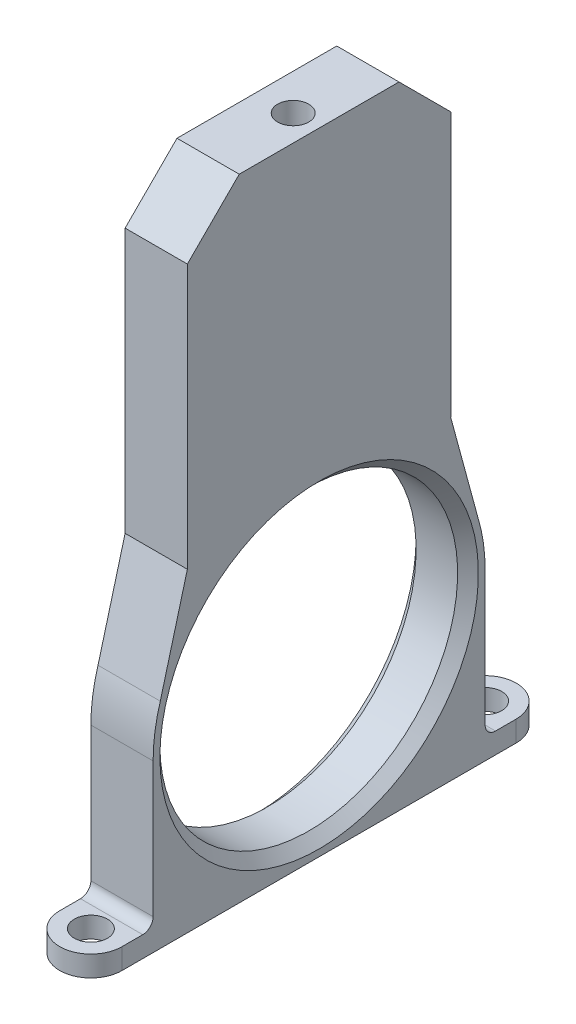
SolidWorks part; units mm, degrees
ref_plane "Front Plane" through (0, 0, 0) normal (0, 0, 1) x (1, 0, 0)
ref_plane "Top Plane" through (0, 0, 0) normal (0, 1, 0) x (1, 0, 0)
ref_plane "Right Plane" through (0, 0, 0) normal (1, 0, 0) x (0, 0, -1)
sketch "Sketch1" plane through (0, 0, 0) normal (0, 1, 0) x (1, 0, 0)
  line L0 (2.5, 12.7) -> (2.5, -12.7)
  line L1 (-55, 0) -> (55, 0) construction
  line L2 (2.5, 12.7) -> (-3.5, 12.7)
  line L3 (-3.5, 12.7) -> (-3.5, -12.7)
  line L4 (-3.5, -12.7) -> (2.5, -12.7)
  circle A0 centre (0, 0) radius 1.5
  point P7 (2.5, 0)
  dimension "D1" = 3
  dimension "D2" = 2.5
  dimension "D3" = 25.4
  dimension "D4" = 6
extrude "Boss-Extrude1" add sketch "Sketch1" along normal blind 30.48
sketch "Sketch2" plane through (0, 0, 0) normal (1, 0, 0) x (0, 0, -1)
  line L0 (-12.7, 0) -> (-15.3112, -9.706)
  line L1 (3.3, 0) -> (-3.3, 0) construction
  line L2 (-12.7, 30.48) -> (-12.7, 0) construction
  line L3 (12.6802, 0) -> (15.3112, -9.706)
  line L4 (16, -14.35) -> (16, -30.35)
  line L5 (16, -30.35) -> (0, -30.35)
  line L6 (0, -30.35) -> (-16, -30.35)
  line L7 (-16, -30.35) -> (-16, -14.35)
  line L9 (-12.7, 0) -> (-12.7, 2.8909)
  line L10 (-12.7, 2.8909) -> (12.7, 2.8909)
  line L11 (12.7, 30.48) -> (12.7, 0) construction
  line L12 (12.7, 2.8909) -> (12.6802, 0)
  circle A1 centre (0, -14.35) radius 14.35
  arc A2 (-15.3112, -9.706) -> (-16, -14.35) centre (0, -14.35) ccw
  arc A3 (16, -14.35) -> (15.3112, -9.706) centre (0, -14.35) ccw
  dimension "D1" = 28.7
  dimension "D2" = 32
sketch "Sketch3" plane through (0, 0, 0) normal (0, -1, 0) x (1, 0, 0)
  circle A0 centre (0, 0) radius 1.5 construction
  circle A1 centre (0, 0) radius 1.5
extrude "Boss-Extrude4" add sketch "Sketch3" against normal blind 2
extrude "Boss-Extrude6" add sketch "Sketch2" along normal up to surface and the other way up to surface up to face at (2.5, 15.24, 0) other way up to face at (-3.5, 15.24, 0)
sketch "Sketch4" plane through (0, -30.35, 0) normal (0, -1, 0) x (1, 0, 0)
  line L0 (2.5, 16) -> (-3.5, 16) construction
  line L1 (-3.5, 16) -> (2.5, 16)
  line L2 (-3.5, 16) -> (-3.5, 19)
  line L3 (2.5, 16) -> (2.5, 19)
  line L4 (3.3, 0) -> (-3.3, 0) construction
  line L5 (2.5, -16) -> (2.5, -19)
  line L6 (-3.5, -16) -> (-3.5, -19)
  line L7 (-3.5, -16) -> (2.5, -16)
  circle A0 centre (-0.5, 19) radius 1.6
  circle A1 centre (-0.5, 19) radius 3
  circle A2 centre (-0.5, -19) radius 1.6
  circle A3 centre (-0.5, -19) radius 3
  point P7 (-0.5, 16)
  line M6 (-3.5, -16) -> (2.5, -16)
  line M8 (2.5, 16) -> (-3.5, 16)
  dimension "D1" = 3.2
  dimension "D3" = 6
  dimension "D2" = 3
extrude "Boss-Extrude7" add sketch "Sketch4" against normal blind 2 contours A1 L3 M8 | A1 L2 L1 | A1 A0 | L7 A3 L5 | L6 A3 M6 | A3 A2 region at (-2.8299, -30.35, 16.6701) region at (1.8299, -30.35, 16.6701) region at (-2.5613, -30.35, 16.9387) region at (1.8299, -30.35, -16.6701) region at (-0.5, -30.35, -21.9151) region at (-2.8299, -30.35, -16.6701)
fillet "Fillet1" radius 1 2 edges at (-0.5, -28.35, -16) (-0.5, -28.35, 16)
chamfer "Chamfer1" distance 5 angle 45 2 edges at (-0.5, 30.48, -12.7) (-0.5, 30.48, 12.7)
chamfer "Chamfer2" distance 1 angle 45 2 edges at (-3.5, -14.35, -14.35) (2.5, -14.35, 14.35)
